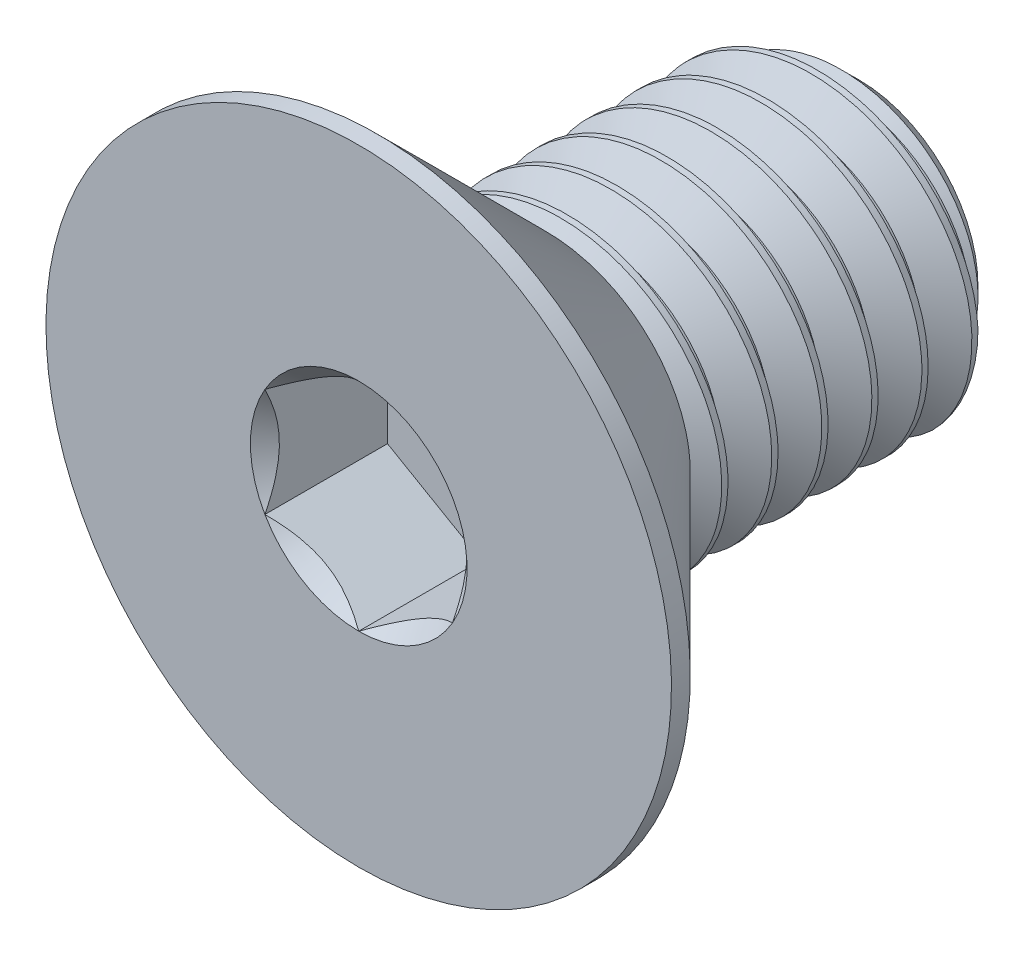
SolidWorks part; units mm, degrees
material "Alloy Steel"
ref_plane "Front" through (0, 0, 0) normal (0, 0, 1) x (1, 0, 0)
ref_plane "Top" through (0, 0, 0) normal (0, 1, 0) x (1, 0, 0)
ref_plane "Right" through (0, 0, 0) normal (1, 0, 0) x (0, 0, -1)
sketch "Sketch1" plane through (0, 0, 0) normal (1, 0, 0) x (0, 0, -1)
  line L0 (0, 5) -> (0.3, 5) construction
  line L1 (0.3, 5) -> (2.8, 2.5) construction
  line L2 (0, 2.5) -> (8, 2.5)
  line L3 (8, 2.5) -> (8, 0)
  line L4 (8, 0) -> (0, 0)
  line L5 (0, 0) -> (0, 5) construction
  line L6 (0, 5) -> (0, -5) construction
  line L7 (8, 2.5) -> (8, -2.5) construction
  line L8 (0, -5) -> (0.3, -5) construction
  line L9 (0.3, -5) -> (2.8, -2.5) construction
  line L11 (0, 2.5) -> (0, 0)
  line L12 (2.8, 2.5) -> (2.8, 0) construction
  dimension "Head Ht" = 2.8
  dimension "Head Dia" = 10
  dimension "Dia" = 5
  dimension "Lg" = 8
  dimension "Head Angle" = 90
revolve "Revolve1" add sketch "Sketch1" angle 360 mid plane about L4
sketch "Sketch3" plane through (0, 0, -8) normal (0, 0, -1) x (-1, 0, 0)
  circle A0 centre (0, 0) radius 2.5
curve "Helix/Spiral1" pitch 0.8 height 8 radius 2.5 centre (0, 0, -8) axis (0, 0, 1) start towards (0, 1, 0)
sketch "Sketch2" plane through (0, 0, 0) normal (1, 0, 0) x (0, 0, -1)
  line L0 (8, 2.5) -> (8.7, 2.5)
  line L1 (8.7, 2.5) -> (8.4, 1.9804)
  line L2 (8.4, 1.9804) -> (8.3, 1.9804)
  line L3 (8.3, 1.9804) -> (8, 2.5)
  line L4 (8.15, 2.2402) -> (8.55, 2.2402) construction
  dimension "D1" = 60
  dimension "D2" = 0.1
  dimension "D3" = 0.4
chamfer "Chamfer1" distance 0.6 angle 45 1 edges at (0, 2.5, -8)
sweep "Cut-Sweep1" cut profiles "Sketch2" path "Helix/Spiral1"
sketch "Sketch7" plane through (0, 0, 0) normal (1, 0, 0) x (0, 0, -1)
  line L0 (0, 5) -> (0.3, 5) construction
  line L1 (0.3, 5) -> (2.8, 2.5) construction
  line L2 (0, 5) -> (0.3, 5)
  line L3 (0.3, 5) -> (2.8, 2.5)
  line L4 (2.8, 2.5) -> (2.8, 0) construction
  line L5 (2.8, 2.5) -> (2.8, 0)
  line L7 (0, 0) -> (0, 5) construction
  line L8 (0, 0) -> (0, 5)
  line L9 (0, 0) -> (2.8, 0)
  line L10 (5.5, 0) -> (-5.5, 0) construction
revolve "Revolve2" add sketch "Sketch7" angle 360 mid plane about L9
ref_plane "Plane1" through (0, 0, -2.8) normal (0, 0, 1) x (1, 0, 0)
sketch "Sketch8" plane through (0, 0, -2.8) normal (0, 0, 1) x (1, 0, 0)
  circle A0 centre (0, 0) radius 2.5
extrude "Boss-Extrude1" add sketch "Sketch8" against normal through all draft 45
sketch "Sketch5" plane through (0, 0, 0) normal (0, 0, 1) x (1, 0, 0)
  line L1 (1.5, -0.866) -> (1.5, 0.866)
  line L2 (1.5, 0.866) -> (0, 1.7321)
  line L3 (0, 1.7321) -> (-1.5, 0.866)
  line L4 (-1.5, 0.866) -> (-1.5, -0.866)
  line L5 (-1.5, -0.866) -> (0, -1.7321)
  line L6 (0, -1.7321) -> (1.5, -0.866)
  circle A0 centre (0, 0) radius 1.5 construction
  dimension "Hex" = 3
extrude "Cut-Extrude2" cut sketch "Sketch5" against normal blind 1.96
sketch "Sketch6" plane through (0, 0, 0) normal (0, 0, 1) x (1, 0, 0)
  circle A0 centre (0, 0) radius 1.7321
extrude "Cut-Extrude3" cut sketch "Sketch6" against normal blind 1.96 draft 45
sketch "Sketch9" [suppressed] plane through (0, 0, -1.5) normal (0, 0, 1) x (1, 0, 0)
  circle A1 centre (0, 0) radius 1.25
  circle A2 centre (0, 0) radius 1.25
  point P0 (0, 1.25)
  dimension "D1" = 0
extrude "Boss-Extrude2" [suppressed] add sketch "Sketch9" against normal offset from surface (3.5 mm away) 26 up to face at (0, 1.9, -8)
fillet "Fillet1" [suppressed] radius 0.5
sketch "Sketch10" plane through (0, 0, 0) normal (1, 0, 0) x (0, 0, -1)
  line L0 (8, 2.5) -> (8, -2.5) construction
  point P0 (6.8, -2.5)
  dimension "D1" = 1.2
equation "\"D3@Helix/Spiral1\" = \"Lg@Sketch1\""
equation "\"D2@Sketch2\" = \"D4@Helix/Spiral1\" * .125"
equation "\"D3@Sketch2\" = \"D4@Helix/Spiral1\" * .5"
equation "\"D1@Chamfer1\" = \"D4@Helix/Spiral1\" * .75"
equation "\"D1@Cut-Extrude2\" = \"Head Ht@Sketch1\" * .7"
equation "\"D1@Sketch10\" = \"D4@Helix/Spiral1\" * 1.5"
equation "\"D1@Cut-Extrude3\" = \"D1@Cut-Extrude2\""
equation "\"D1@Fillet1\" = \"Dia@Sketch1\" * .1"
